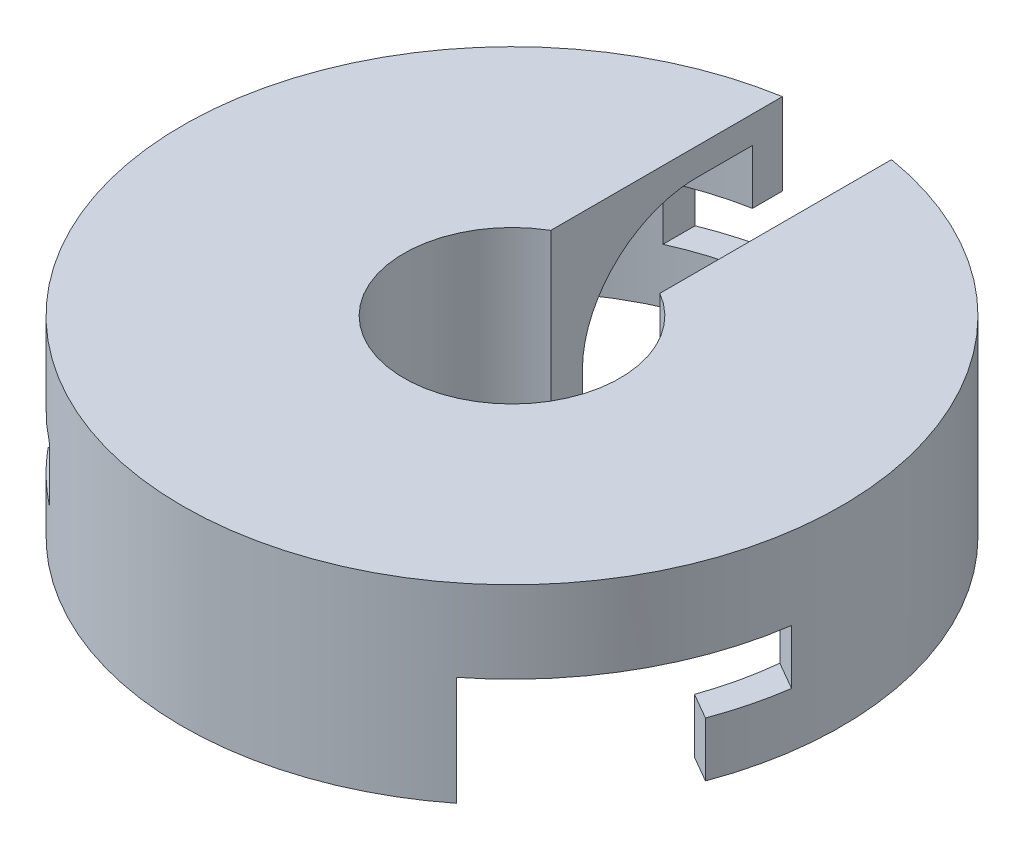
SolidWorks part; units mm, degrees
note: The reader was unsure of these and kept them because the rebuilt part matched: shared geometry of "Sketch1<6>", "Sketch1<7>", "Sketch1<8>", "Sketch1<9>".
ref_plane "Front Plane" through (0, 0, 0) normal (0, 0, 1) x (1, 0, 0)
ref_plane "Top Plane" through (0, 0, 0) normal (0, 1, 0) x (1, 0, 0)
ref_plane "Right Plane" through (0, 0, 0) normal (1, 0, 0) x (0, 0, -1)
sketch "Sketch1" plane through (0, 0, 0) normal (0, 1, 0) x (1, 0, 0)
  line L0 (0, 0) -> (0, 22) construction
  line L1 (17.4054, -4.8529) -> (10.9427, -1.1216)
  line L2 (12.9054, -12.6471) -> (6.4427, -8.9158)
  line L3 (-4.5, 17.5) -> (-4.5, 10.0374)
  line L4 (4.5, 17.5) -> (4.5, 10.0374)
  line L5 (-12.9054, -12.6471) -> (-6.4427, -8.9158)
  line L6 (-17.4054, -4.8529) -> (-10.9427, -1.1216)
  line L7 (-2, 11.9156) -> (-2, 3.4223)
  line L8 (2, 11.9156) -> (2, 3.4223)
  line L9 (11.3192, -4.2258) -> (3.9638, 0.0209)
  line L10 (-9.3192, -7.6899) -> (-1.9638, -3.4432)
  line L11 (-2, 7.669) -> (2, 7.669) construction
  circle A0 centre (0, 0) radius 22
  circle A1 centre (0, 0) radius 11
  circle A2 centre (0, 0) radius 3.9639
  circle A3 centre (0, 0) radius 17.5 construction
  arc A4 (12.9054, -12.6471) -> (17.4054, -4.8529) centre (15.1554, -8.75) ccw
  circle A5 centre (15.1554, -8.75) radius 2.75 construction
  circle A6 centre (0, 17.5) radius 2.75 construction
  arc A7 (-17.4054, -4.8529) -> (-12.9054, -12.6471) centre (-15.1554, -8.75) ccw
  circle A8 centre (-15.1554, -8.75) radius 2.75 construction
  arc A9 (4.5, 17.5) -> (-4.5, 17.5) centre (0, 17.5) ccw
  circle A10 centre (0, 0) radius 12.0823
  circle A11 centre (-15.1554, -8.75) radius 2.75
  circle A12 centre (0, 17.5) radius 2.75
  circle A13 centre (15.1554, -8.75) radius 2.75
  circle A14 centre (0, 0) radius 5
  point P8 (0, 0)
  point P9 (0, 17.5)
  point P29 (0, 0)
  point P39 (0, 7.669)
  point P44 (0, 0)
  point P45 (0, 7.669)
  dimension "D1" = 3
  dimension "D2" = 3
  dimension "D3" = 4
extrude "Boss-Extrude3" add sketch "Sketch1" against normal blind 7 contours A14 A2 | L9 A14 L8 A2 | L7 A14 L10 A2
extrude "Boss-Extrude4" add sketch "Sketch1<6>" against normal blind 1 contours A14 L10 A1 L9 | A14 L7 A1 L10 | A14 L9 A1 L8 | A10
sketch "Sketch1<6>" plane through (0, 0, 0) normal (0, 1, 0) x (1, 0, 0) same geometry as "Sketch1"
extrude "Boss-Extrude5" add sketch "Sketch1<7>" against normal blind 7 contours L5 A10 L2 A1 | L1 A10 L4 A1 | L3 A10 L6 A1
sketch "Sketch1<7>" plane through (0, 0, 0) normal (0, 1, 0) x (1, 0, 0) same geometry as "Sketch1"
extrude "Boss-Extrude6" add sketch "Sketch1<8>" against normal blind 3 contours L6 A10 L5 A1 | L2 A10 L1 A1 | L7 A10 L3 A1 | L4 A10 L8 A1 | L10 A10 L5 A1 | L9 A10 L1 A1
sketch "Sketch1<8>" plane through (0, 0, 0) normal (0, 1, 0) x (1, 0, 0) same geometry as "Sketch1"
extrude "Boss-Extrude7" add sketch "Sketch1<9>" against normal blind 2 from offset 5 contours L10 A10 L5 A1 | L9 A10 L1 A1 | L7 A10 L3 A1 offset against normal yes
sketch "Sketch1<9>" plane through (0, 0, 0) normal (0, 1, 0) x (1, 0, 0) same geometry as "Sketch1"
fillet "Fillet1" radius 4 1 edges at (0, -1, 5)
